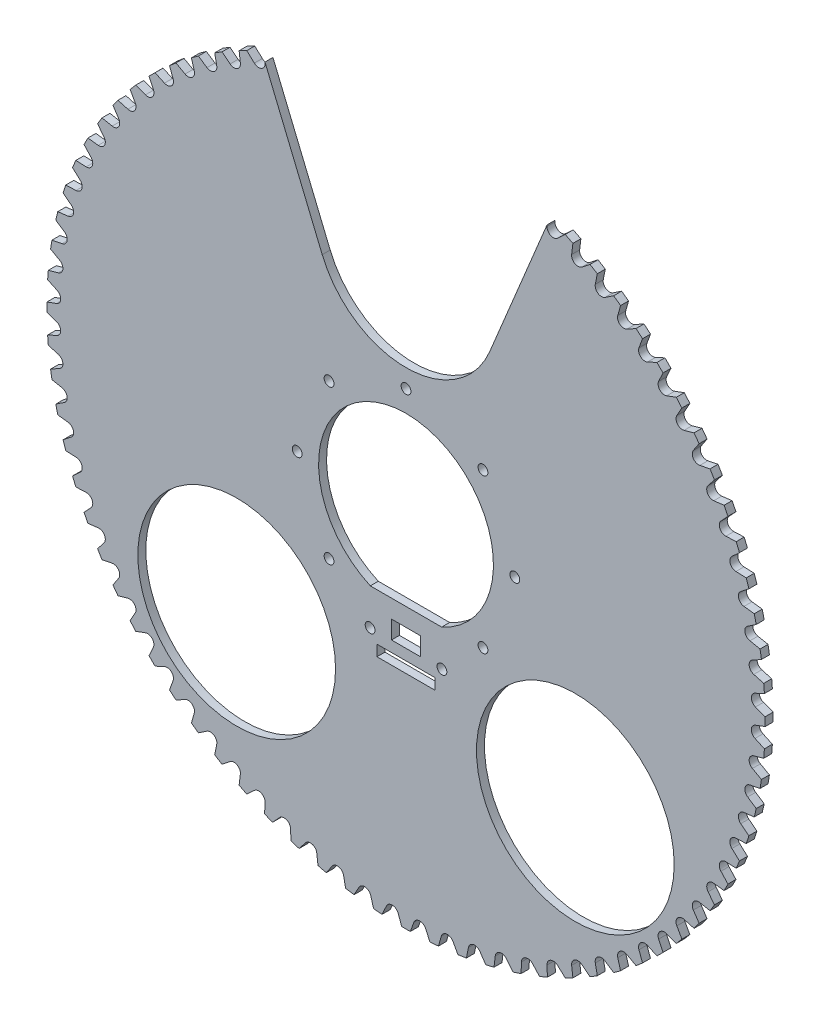
SolidWorks part; units mm, degrees
note: '?' marks a value the reader was unsure of.
ref_plane "Front Plane" through (0, 0, 0) normal (0, 0, 1) x (1, 0, 0)
ref_plane "Top Plane" through (0, 0, 0) normal (0, 1, 0) x (1, 0, 0)
ref_plane "Right Plane" through (0, 0, 0) normal (1, 0, 0) x (0, 0, -1)
ref_axis "Axis1" through (0, 0, 2.625) along (0, 0, -1)?
sketch "Esquisse1" plane through (0, 0, 0) normal (0, 0, 1) x (1, 0, 0)
  line L0 (-9.8392, -22) -> (9.8392, -22)
  circle A0 centre (0, 0) radius 99
  arc A1 (9.8392, -22) -> (-9.8392, -22) centre (0, 0) ccw
  dimension "D1" = 198
  dimension "D2" = 24.1
  dimension "D3" = 22
extrude "Main" add sketch "Esquisse1" along normal blind 2.2
sketch "Esquisse2" plane through (0, 0, 2.2) normal (0, 0, 1) x (1, 0, 0)
  line L0 (-23.097, 50.4329) -> (-39.7614, 90.6644)
  line L1 (23.097, 50.4329) -> (39.7614, 90.6644)
  line L2 (0, 0) -> (0, -112.8607) construction
  line L3 (-46.669, -46.669) -> (0, 0) construction
  line L4 (-9.9, -32) -> (9.9, -32) construction
  line L5 (-4, -27) -> (4, -27)
  line L6 (-4, -27) -> (-4, -32)
  line L7 (-4, -32) -> (4, -32)
  line L8 (4, -27) -> (4, -32)
  line L12 (-8, -35) -> (8, -35)
  line L13 (-8, -35) -> (-8, -38)
  line L14 (-8, -38) -> (8, -38)
  line L15 (8, -35) -> (8, -38)
  arc A0 (-23.097, 50.4329) -> (23.097, 50.4329) centre (0, 60) ccw
  circle A1 centre (0, 0) radius 99 construction
  circle A2 centre (-46.669, -46.669) radius 27.25
  circle A3 centre (46.669, -46.669) radius 27.25
  arc A4 (-39.7614, 90.6644) -> (39.7614, 90.6644) centre (0, 0) cw
  circle A5 centre (-9.9, -32) radius 1.35
  circle A6 centre (9.9, -32) radius 1.35
  point P12 (0, -32)
  point P24 (0, -32)
  point P30 (0, -35)
  point P31 (0, -27)
  dimension "D2" = 25
  dimension "D4" = 54.5
  dimension "D12" = 2.7
  dimension "D1" = 45
  dimension "D3" = 60
  dimension "D5" = 45
  dimension "D6" = 90
  dimension "D7" = 66
  dimension "D8" = 8
  dimension "D9" = 5
  dimension "D10" = 32
  dimension "D11" = 19.8
  dimension "D13" = 3
  dimension "D14" = 3
  dimension "D15" = 16
extrude "Holes" cut sketch "Esquisse2" against normal through all and the other way through all
sketch "Sketch1" plane through (0, 0, 2.2) normal (0, 0, 1) x (1, 0, 0)
  circle A0 centre (30, 0) radius 1.35
  dimension "D1" = 2.7
  dimension "D2" = 30
extrude "FixingHoles" cut sketch "Sketch1" against normal through all
pattern_circular "CirPattern1" count 6 every 45 about axis through (0, 0, 0) along (0, 0, 1) of "FixingHoles"
sketch "Sketch2" plane through (0, 0, 2.2) normal (0, 0, 1) x (1, 0, 0)
  line L0 (96.1926, 5.3975) -> (98.7804, 6.5905)
  line L1 (96.3195, 2.1664) -> (98.993, 1.1801)
  line L2 (0, 0) -> (96.9252, 3.8082) construction
  line L3 (96.1926, 5.3975) -> (96.3195, 2.1664) construction
  line L4 (0, 0) -> (110.3009, 0) construction
  arc A0 (96.1926, 5.3975) -> (96.3195, 2.1664) centre (96.9252, 3.8082) ccw
  arc A2 (98.993, 1.1801) -> (98.7804, 6.5905) centre (0, 0) ccw
  arc A3 (-39.7614, 90.6644) -> (39.7614, 90.6644) centre (0, 0) ccw construction
  dimension "D1" = 1.75
  dimension "D2" = 45
  dimension "D3" = 97
  dimension "D4" = 2.25
extrude "Cut-Extrude3" cut sketch "Sketch2" against normal through all
pattern_circular "CirPattern2" count 80 over 360 about axis through (0, 0, 0) along (0, 0, 1) of "Cut-Extrude3"
pattern_circular "CirPattern3" count 2 every 45 about axis through (0, 0, 2.625) along (0, 0, -1) of "FixingHoles"
